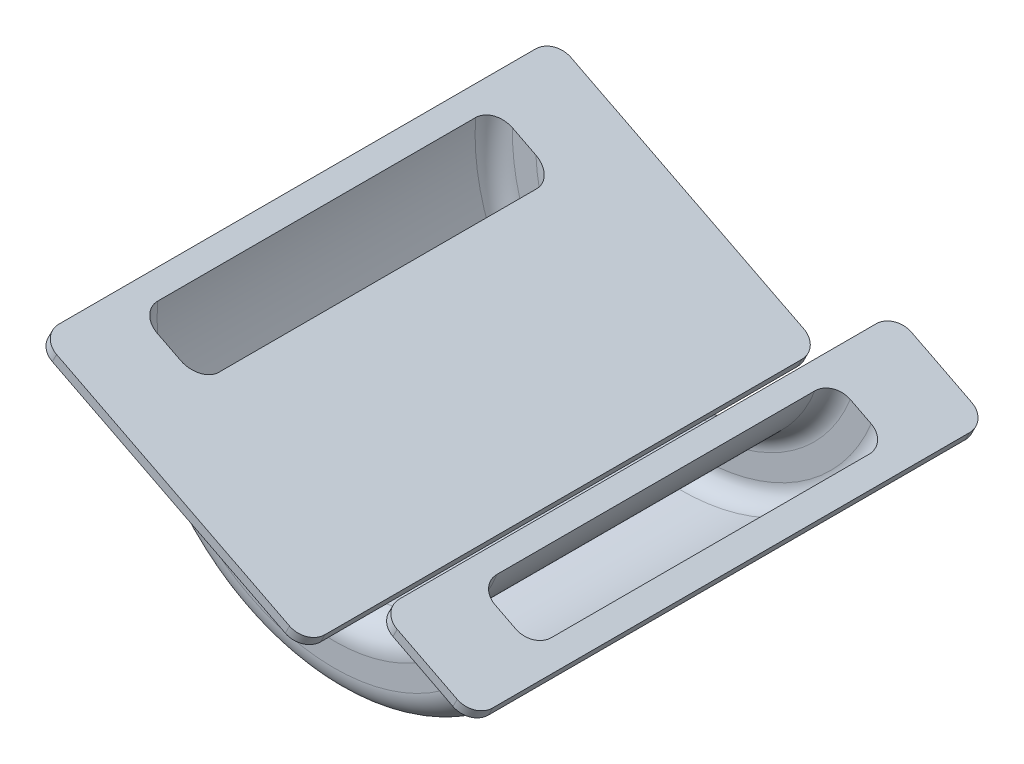
SolidWorks part; units mm, degrees
ref_plane "Front Plane" through (0, 0, 0) normal (0, 0, 1) x (1, 0, 0)
ref_plane "Top Plane" through (0, 0, 0) normal (0, 1, 0) x (1, 0, 0)
ref_plane "Right Plane" through (0, 0, 0) normal (1, 0, 0) x (0, 0, -1)
sketch "Sketch9" plane through (0, 0, 0) normal (0, 0, 1) x (1, 0, 0)
  line L0 (-39.9175, 679.141) -> (10.8017, 653.2983) construction
  line L2 (-39.9175, 679.141) -> (10.8017, 653.2983)
extrude "Extrude-Thin1" add sketch "Sketch9" along normal blind 76.2 and the other way blind 203.2 thin thin type one direction wall 5.08
sketch "Sketch10" plane through (0, 0, 0) normal (0, 0, 1) x (1, 0, 0)
  line L0 (-224.9173, 715.9235) -> (-128.8179, 666.9584) construction
  line L1 (-224.9173, 715.9235) -> (-80.2857, 642.23)
  dimension "D1" = 73.6935
extrude "Extrude-Thin2" add sketch "Sketch10" along normal blind 76.2 and the other way blind 203.2 separate body thin thin type one direction wall 5.08
ref_plane "Plane1" through (0, 0, -63.5) normal (0, 0, 1) x (1, 0, 0)
sketch "Sketch11" plane through (0, 0, -63.5) normal (0, 0, 1) x (1, 0, 0)
  line L0 (-227.2236, 711.3972) -> (-82.5919, 637.7037) construction
  line L1 (-42.2237, 674.6147) -> (8.4954, 648.772) construction
  line L2 (-219.5826, 707.5039) -> (-174.3194, 684.4412)
  line L3 (-36.5658, 671.7319) -> (1.9078, 652.1286)
  arc A0 (-174.3194, 684.4412) -> (-36.5658, 671.7319) centre (-103.2043, 702.3474) ccw
  arc A2 (1.9078, 652.1286) -> (-219.5826, 707.5039) centre (-103.2043, 702.3474) cw
  dimension "D1" = 8.5758
  dimension "D2" = 50.8
  dimension "D3" = 6.35
  dimension "D4" = 43.18
extrude "Boss-Extrude1" add sketch "Sketch11" along normal mid plane 203.2
fillet "Fillet1" radius 15.24 4 edges at (-109.9416, 629.3227, 38.1) (-131.4592, 589.3335, 38.1) (-109.9416, 629.3227, -165.1) (-131.4592, 589.3335, -165.1)
fillet "Fillet4" radius 10.16 8 edges at (-226.0705, 713.6604, 76.2) (-81.4388, 639.9669, 76.2) (-41.0706, 676.8779, 76.2) (9.6485, 651.0352, 76.2) (9.6485, 651.0352, -203.2) (-41.0706, 676.8779, -203.2) (-226.0705, 713.6604, -203.2) (-81.4388, 639.9669, -203.2)
shell "Shell1" thickness 5.08 removed face at (-197.1224, 696.0599, -63.4994) removed face at (-152.6015, 679.0768, -63.5) removed face at (-14.5579, 666.2197, -63.5)
fillet "Fillet5" radius 5.08 16 edges at (-17.3269, 661.9292, -165.1) (-1.067, 653.6443, -159.3779) (-3.1877, 654.7249, 34.7583) (-17.3269, 661.9292, 38.1) (-33.5919, 670.2166, 32.3747) (-36.5658, 671.7319, -63.5) (-197.8591, 696.4353, -165.1) (-176.8952, 685.7536, -157.7498) (-174.3194, 684.4412, -63.5) (-178.7838, 686.7159, 32.979) (-197.8591, 696.4353, 38.1) (-216.7963, 706.0843, 31.7184) (-219.5826, 707.5039, -63.5) (-31.4698, 669.1353, -161.7567) (-214.8834, 705.1096, -160.9428) (1.9078, 652.1286, -63.5)
sketch "Sketch13" plane through (0, 0, -63.5) normal (0, 0, 1) x (1, 0, 0)
  line L1 (-957.4681, 2.9594) -> (-808.2143, 2.9594)
  line L2 (-957.4681, 2.9594) -> (-957.4681, -239.9725)
  line L3 (-957.4681, -239.9725) -> (-808.2143, -239.9725)
  line L4 (-808.2143, 2.9594) -> (-808.2143, -239.9725)
  dimension "D1" = 149.2538
  dimension "D2" = 242.9318
extrude "Boss-Extrude2" [suppressed] add sketch "Sketch13" along normal mid plane 289.306
